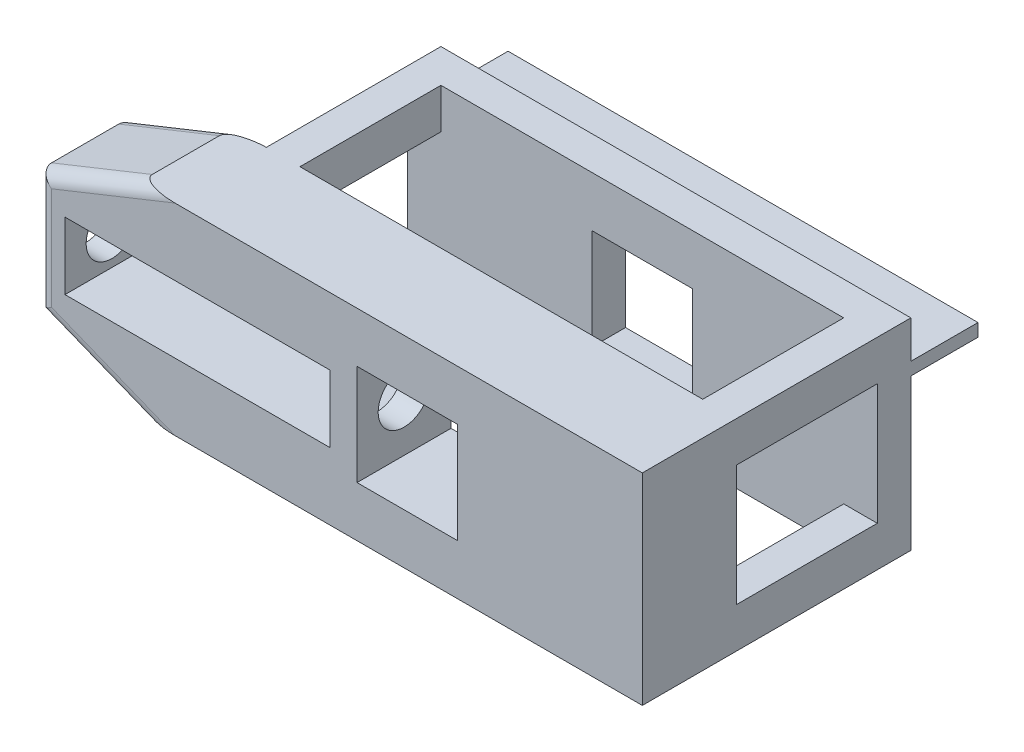
SolidWorks part; units mm, degrees
other "Markup1"
sketch "Sketch12" plane through (0, 38.1, 0) normal (-0.0705, 0.1614, 0.9844) x (0.9933, -0.0793, 0.0841)
material "ABS"
ref_plane "Front Plane" through (0, 0, 0) normal (0, 0, 1) x (1, 0, 0)
ref_plane "Top Plane" through (0, 0, 0) normal (0, 1, 0) x (1, 0, 0)
ref_plane "Right Plane" through (0, 0, 0) normal (1, 0, 0) x (0, 0, -1)
sketch "Sketch1" plane through (0, 0, 0) normal (0, 0, 1) x (1, 0, 0)
  line L1 (0, 0) -> (88.9, 0)
  line L2 (0, 0) -> (0, 38.1)
  line L3 (0, 38.1) -> (88.9, 38.1)
  line L4 (88.9, 0) -> (88.9, 38.1)
  line L5 (0, 0) -> (-25.4, 0)
  line L6 (0, 0) -> (0, 38.1)
  line L7 (0, 38.1) -> (-25.4, 38.1)
  line L8 (-25.4, 0) -> (-25.4, 38.1)
  dimension "D1" = 88.9
  dimension "D2" = 38.1
extrude "Boss-Extrude1" add sketch "Sketch1" against normal blind 17.78 contours L1 L4 L3 L2 | L8 L5 L2 L7 region at (44.45, 19.05, 0) region at (-12.7, 19.05, 0)
sketch "Sketch2" plane through (0, 0, 0) normal (0, 0, 1) x (1, 0, 0)
  line L0 (0, 19.05) -> (88.9, 19.05) construction
  line L1 (0, 0) -> (0, 38.1) construction
  line L2 (88.9, 0) -> (88.9, 38.1) construction
  line L3 (44.45, 0) -> (44.45, 38.1) construction
  line L4 (0, 0) -> (88.9, 0) construction
  line L5 (0, 38.1) -> (88.9, 38.1) construction
  line L6 (88.9, 30.48) -> (82.55, 30.48)
  line L7 (34.925, 28.575) -> (53.975, 28.575)
  line L8 (34.925, 28.575) -> (34.925, 9.525)
  line L9 (34.925, 9.525) -> (53.975, 9.525)
  line L10 (53.975, 28.575) -> (53.975, 9.525)
  line L11 (0, 38.1) -> (6.35, 38.1)
  line L12 (0, 38.1) -> (0, 30.48)
  line L13 (0, 30.48) -> (6.35, 30.48)
  line L14 (6.35, 38.1) -> (6.35, 30.48)
  line L15 (82.55, 38.1) -> (82.55, 30.48)
  line L16 (88.9, 38.1) -> (82.55, 38.1)
  line L17 (88.9, 38.1) -> (88.9, 30.48)
  line L18 (88.9, 0) -> (88.9, 7.62)
  line L19 (88.9, 0) -> (82.55, 0)
  line L20 (82.55, 0) -> (82.55, 7.62)
  line L21 (88.9, 7.62) -> (82.55, 7.62)
  line L22 (0, 7.62) -> (6.35, 7.62)
  line L23 (6.35, 0) -> (6.35, 7.62)
  line L24 (0, 0) -> (6.35, 0)
  line L25 (0, 0) -> (0, 7.62)
  line L26 (-25.4, 0) -> (-25.4, 38.1) construction
  line L27 (29.845, 25.4) -> (-8.255, 25.4)
  line L28 (29.845, 25.4) -> (29.845, 12.7)
  line L29 (29.845, 12.7) -> (-8.255, 12.7)
  line L30 (-8.255, 25.4) -> (-8.255, 12.7)
  line L31 (-25.4, 38.1) -> (88.9, 38.1) construction
  line L32 (-8.255, 25.4) -> (-20.32, 25.4)
  line L33 (-8.255, 25.4) -> (-8.255, 12.7)
  line L34 (-8.255, 12.7) -> (-20.32, 12.7)
  line L35 (-20.32, 25.4) -> (-20.32, 12.7)
  dimension "D1" = 19.05
  dimension "D3" = 34.925
  dimension "D7" = 6.35
  dimension "D10" = 12.7
  dimension "D2" = 19.05
  dimension "D4" = 9.525
  dimension "D11" = 6.35
  dimension "D8" = 5.08
  dimension "D9" = 38.1
  dimension "D5" = 7.62
  dimension "D6" = 5.08
extrude "Cut-Extrude1" cut sketch "Sketch2" against normal blind 41.402 contours L27 L30 L29 L28 | L14 L11 L12 L13 | L25 L24 L23 L22 | L10 L7 L8 L9 | L17 L16 L15 L6 | L18 L21 L20 L19 | L33 L32 L35 L34 region at (85.725, 34.29, 0) region at (44.45, 19.05, 0) region at (3.175, 34.29, 0) region at (85.725, 3.81, 0) region at (3.175, 3.81, 0) region at (10.795, 19.05, 0)
ref_plane "Plane1" through (0, 0, -50.8) normal (0, 0, 1) x (1, 0, 0)
sketch "Sketch3" plane through (0, 0, -50.8) normal (0, 0, 1) x (1, 0, 0)
  line L4 (34.925, 9.525) -> (53.975, 9.525)
  line L5 (53.975, 9.525) -> (53.975, 28.575)
  line L6 (53.975, 28.575) -> (34.925, 28.575)
  line L7 (34.925, 28.575) -> (34.925, 9.525)
  line L8 (0, 0) -> (0, 38.1)
  line L94 (88.9, 30.48) -> (82.55, 30.48)
  line L96 (88.9, 7.62) -> (88.9, 30.48)
  line L98 (82.55, 7.62) -> (88.9, 7.62)
  line L104 (82.55, 0) -> (82.55, 7.62)
  line L105 (6.35, 0) -> (82.55, 0)
  line L106 (6.35, 7.62) -> (6.35, 0)
  line L107 (0, 7.62) -> (6.35, 7.62)
  line L108 (0, 0) -> (0, 7.62)
  line L109 (-25.4, 0) -> (0, 0)
  line L110 (-25.4, 38.1) -> (-25.4, 0)
  line L111 (0, 38.1) -> (-25.4, 38.1)
  line L112 (0, 30.48) -> (0, 38.1)
  line L113 (6.35, 30.48) -> (0, 30.48)
  line L114 (6.35, 38.1) -> (6.35, 30.48)
  line L115 (82.55, 38.1) -> (6.35, 38.1)
  line L116 (82.55, 30.48) -> (82.55, 38.1)
  line L117 (88.9, 30.48) -> (82.55, 30.48)
  line L118 (88.9, 7.62) -> (88.9, 30.48)
  line L119 (82.55, 7.62) -> (88.9, 7.62)
  line L120 (82.55, 0) -> (82.55, 7.62)
  line L121 (6.35, 0) -> (82.55, 0)
  line L122 (6.35, 7.62) -> (6.35, 0)
  line L123 (0, 7.62) -> (6.35, 7.62)
  line L124 (0, 0) -> (0, 7.62)
  line L125 (-25.4, 0) -> (0, 0)
  line L126 (-25.4, 38.1) -> (-25.4, 0)
  line L127 (0, 38.1) -> (-25.4, 38.1)
  line L128 (0, 30.48) -> (0, 38.1)
  line L129 (6.35, 30.48) -> (0, 30.48)
  line L130 (6.35, 38.1) -> (6.35, 30.48)
  line L131 (82.55, 38.1) -> (6.35, 38.1)
  line L132 (82.55, 30.48) -> (82.55, 38.1)
  dimension "D2" = 9.525
  dimension "D3" = 9.525
  dimension "D4" = 19.05
  dimension "D5" = 28.575
  dimension "D6" = 19.05
  dimension "D1" = 0
extrude "Boss-Extrude2" add sketch "Sketch3" along normal blind 6.35 contours L117 L132 L131 L130 L129 L8 L123 L122 L121 L120 L119 L118 L7 L6 L5 L4 region at (0.9672, 19.05, -50.8)
sketch "Sketch6" plane through (-25.4, 0, 0) normal (-1, 0, 0) x (0, 0, 1)
  line L5 (-17.78, 25.4) -> (-17.78, 12.7)
  line L6 (-17.78, 12.7) -> (0, 12.7)
  line L7 (-17.78, 25.4) -> (-17.78, 12.7)
  line L8 (0, 25.4) -> (-17.78, 25.4)
  line L9 (0, 12.7) -> (0, 25.4)
  line L10 (-17.78, 12.7) -> (0, 12.7)
  line L12 (0, 25.4) -> (-17.78, 25.4)
  line L14 (0, 12.7) -> (0, 25.4)
  circle A0 centre (-8.89, 19.05) radius 4.8895
  dimension "D2" = 9.779
  dimension "D5" = 12.7
  dimension "D3" = 6.35
  dimension "D1" = 8.89
extrude "SpringPlunger Hole" cut sketch "Sketch6" against normal blind 89.916 contours A0
sketch "Sketch8" plane through (0, 0, 0) normal (0, 0, 1) x (1, 0, 0)
  line L30 (0, 0) -> (0, 38.1) construction
  line L31 (0, 38.1) -> (6.35, 38.1)
  line L32 (0, 38.1) -> (0, 30.1625)
  line L33 (0, 30.1625) -> (6.35, 30.1625)
  line L34 (6.35, 38.1) -> (6.35, 30.1625)
  line L35 (82.55, 38.1) -> (88.9, 38.1)
  line L36 (82.55, 38.1) -> (82.55, 30.1625)
  line L37 (82.55, 30.1625) -> (88.9, 30.1625)
  line L38 (88.9, 38.1) -> (88.9, 30.1625)
  line L39 (82.55, 7.9375) -> (88.9, 7.9375)
  line L40 (82.55, 7.9375) -> (82.55, 0)
  line L41 (82.55, 0) -> (88.9, 0)
  line L42 (88.9, 7.9375) -> (88.9, 0)
  line L43 (0, 7.9375) -> (6.35, 7.9375)
  line L44 (0, 7.9375) -> (0, 0)
  line L45 (0, 0) -> (6.35, 0)
  line L46 (6.35, 7.9375) -> (6.35, 0)
  line L48 (0, 0) -> (88.9, 0) construction
extrude "Support" add sketch "Sketch8" against normal up to surface (50.8 mm away) up to face at (44.45, 19.05, -50.8)
sketch "Sketch9" plane through (29.845, 0, 0) normal (-1, 0, 0) x (0, 0, 1)
  circle A3 centre (-8.89, 19.05) radius 4.8895
  dimension "D2" = 9.779
extrude "Cut-Extrude4" [suppressed] cut sketch "Sketch9" against normal up to surface (5.08 mm away) up to face at (34.925, 19.05, -4.0005)
sketch "Sketch10" plane through (0, 0, -50.8) normal (0, 0, -1) x (-1, 0, 0)
  line L1 (-88.9, 30.988) -> (0, 30.988)
  line L2 (-88.9, 30.988) -> (-88.9, 28.575)
  line L3 (-88.9, 28.575) -> (0, 28.575)
  line L4 (0, 30.988) -> (0, 28.575)
  line L8 (-88.9, 38.1) -> (0, 38.1) construction
  line L10 (-88.9, 0) -> (-88.9, 38.1) construction
  dimension "D1" = 7.112
  dimension "D2" = 88.9
  dimension "D3" = 2.413
extrude "Boss-Extrude3" add sketch "Sketch10" along normal blind 12.7
sketch "Sketch11" [suppressed] plane through (0, 0, 0) normal (0, 0, 1) x (1, 0, 0)
  line L0 (88.9, 0) -> (88.9, 38.1) construction
  line L1 (60.325, 27.94) -> (82.55, 27.94)
  line L2 (60.325, 27.94) -> (60.325, 6.35)
  line L3 (60.325, 6.35) -> (82.55, 6.35)
  line L4 (82.55, 27.94) -> (82.55, 6.35)
  line L5 (53.975, 28.575) -> (53.975, 9.525) construction
  line L6 (0, 38.1) -> (88.9, 38.1) construction
  line L7 (0, 0) -> (88.9, 0) construction
  dimension "D1" = 6.35
  dimension "D2" = 6.35
  dimension "D3" = 10.16
  dimension "D4" = 6.35
sketch "Sketch13" plane through (0, 0, 0) normal (0, 0, 1) x (1, 0, 0)
  line L0 (-6.35, 38.1) -> (-25.4, 30.48)
  line L1 (-25.4, 0) -> (-25.4, 38.1) construction
  line L2 (-6.35, 38.1) -> (-25.4, 38.1)
  line L3 (-25.4, 38.1) -> (-25.4, 30.48)
  line L4 (-6.35, 0) -> (-25.4, 0)
  line L5 (-25.4, 0) -> (-25.4, 7.62)
  line L6 (-25.4, 7.62) -> (-6.35, 0)
  line L7 (-25.4, 0) -> (88.9, 0) construction
  line M4 (88.9, 38.1) -> (-25.4, 38.1)
  line M5 (-25.4, 38.1) -> (-25.4, 0)
  line M6 (-25.4, 0) -> (88.9, 0)
  dimension "D1" = 7.62
  dimension "D2" = 7.62
  dimension "D3" = 6.35
  dimension "D4" = 6.35
extrude "Cut-Extrude5" cut sketch "Sketch13" against normal up to surface (17.78 mm away) contours L0 M4 M5 | L6 M5 M6 region at (-19.05, 2.54, 0) region at (-19.05, 35.56, 0) up to face at (44.45, 19.05, -17.78)
fillet "Fillet1" radius 2.54 6 edges at (-15.875, 3.81, 0) (-15.875, 3.81, -17.78) (-15.875, 34.29, -17.78) (-15.875, 34.29, 0) (-25.4, 19.05, 0) (-25.4, 19.05, -17.78)
equation "\"box\"= 3.5"
equation "\"D1@Sketch1\"=\"box\""
equation "\"shaft\"= .75"
equation "\"D1@Sketch2\"=\"shaft\""
equation "\"D3@Sketch2\"=(\"box\"-\"shaft\")/2"
equation "\"D7@Sketch2\"=0.25"
equation "\"springHole\"=1"
equation "\"depth1\"=0.7"
equation "\"D1@Boss-Extrude1\"=\"depth1\""
equation "\"springShaftD\"=0.385"
equation "\"D2@Sketch6\"=\"springShaftD\""
equation "\"D2@Sketch1\"=(\"box\"/3.5)*1.5"
equation "\"D2@Sketch2\"=\"shaft\""
equation "\"D4@Sketch2\"=\"shaft\"/2"
equation "\"D11@Sketch2\"=\"D10@Sketch2\"/2"
equation "\"D3@Sketch6\"=\"D5@Sketch6\"/2"
equation "\"springPinD\"=0.385"
equation "\"D2@Sketch9\"=\"springPinD\""
